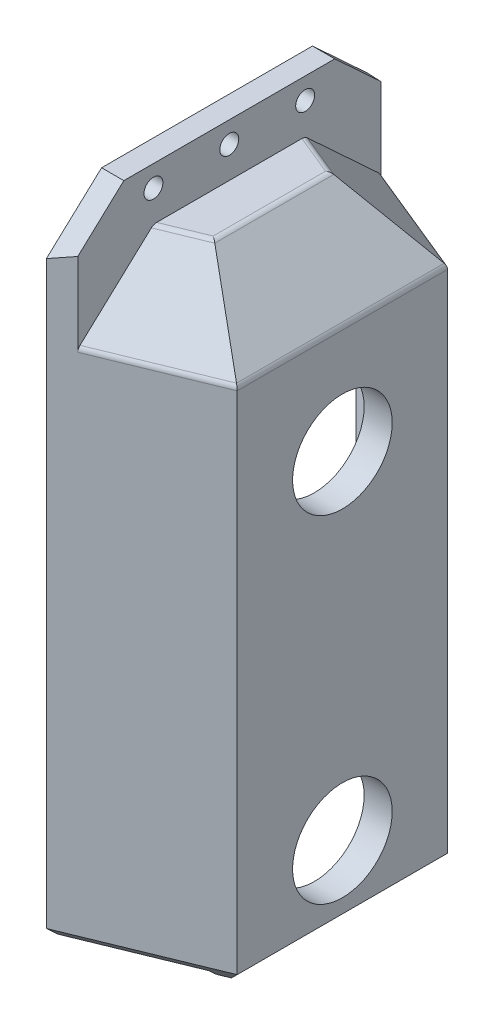
SolidWorks part; units mm, degrees
material "PLA"
ref_plane "Front Plane" through (0, 0, 0) normal (0, 0, 1) x (1, 0, 0)
ref_plane "Top Plane" through (0, 0, 0) normal (0, 1, 0) x (1, 0, 0)
ref_plane "Right Plane" through (0, 0, 0) normal (1, 0, 0) x (0, 0, -1)
sketch "Sketch1" plane through (0, 0, 0) normal (1, 0, 0) x (0, 0, -1)
  line L1 (-15, 2.5) -> (15, 2.5)
  line L2 (-15, 2.5) -> (-15, -2.5)
  line L3 (-15, -2.5) -> (15, -2.5)
  line L4 (15, 2.5) -> (15, -2.5)
  point P4 (0, 2.5)
  point P6 (-15, 0)
  dimension "D1" = 30
  dimension "D2" = 5
extrude "Boss-Extrude1" add sketch "Sketch1" along normal blind 19.3
sketch "Sketch2" plane through (0, 0, 0) normal (-1, 0, 0) x (0, 0, 1)
  line L0 (-20.4312, -2.5) -> (20.4312, -2.5) construction
  line L4 (15, 0) -> (20.5974, 0) construction
  line L5 (-19.4026, -2.5) -> (20.5974, -2.5)
  line L7 (-19.4026, 7.5) -> (20.5974, 7.5)
  line L8 (20.5974, -2.5) -> (20.5974, 7.5)
  line L9 (-19.4026, 7.5) -> (-19.4026, 2.5) construction
  line L11 (-19.4026, 7.5) -> (-19.4026, -2.5)
  line L12 (-19.4026, 0) -> (-15, 0) construction
  line L13 (-15, -2.5) -> (-15, 2.5) construction
  line L14 (15, 2.5) -> (15, -2.5) construction
  line L15 (-19.4026, 5) -> (0, 5) construction
  line L16 (20.5974, 5) -> (0, 5) construction
  point P3 (0, -2.5)
  point P6 (0, 2.5)
  point P12 (0, 0)
  dimension "D1" = 10
  dimension "D2" = 40
extrude "Boss-Extrude2" add sketch "Sketch2" against normal blind 3.175
sketch "Sketch3" plane through (0, -2.5, 0) normal (0, -1, 0) x (1, 0, 0)
  line L0 (19.3, -15) -> (3.175, -15) construction
  line L1 (19.3, 15) -> (15.3, 15)
  line L2 (19.3, 15) -> (19.3, -15)
  line L3 (19.3, -15) -> (15.3, -15)
  line L4 (15.3, 15) -> (15.3, -15)
  dimension "D1" = 4
extrude "Boss-Extrude3" add sketch "Sketch3" along normal blind 75
sketch "Sketch4" plane through (19.3, 0, 0) normal (1, 0, 0) x (0, 0, -1)
  line L0 (15, 2.5) -> (-15, 2.5) construction
  circle A0 centre (0, -17.9) radius 7.1
  circle A1 centre (0, -65.9) radius 7.1
  dimension "D1" = 14.2
  dimension "D2" = 14.2
  dimension "D3" = 20.4
  dimension "D4" = 48
extrude "Cut-Extrude1" cut sketch "Sketch4" against normal up to next
sketch "Sketch10" plane through (0, 2.5, 0) normal (0, 1, 0) x (1, 0, 0)
  line L0 (3.175, 19.4026) -> (0, 19.4026)
  line L1 (0, 19.4026) -> (0, 22.9026)
  line L2 (0, 22.9026) -> (19.3, 15)
  line L3 (19.3, 15) -> (3.175, 15) construction
  line L4 (19.3, 15) -> (19.3, -15) construction
  line L5 (3.175, 19.4026) -> (3.175, 15)
  line L6 (3.175, 15) -> (19.3, 15)
  dimension "D1" = 3.5
extrude "Boss-Extrude7" add sketch "Sketch10" against normal up to surface (5 mm away) up to face at (5.4125, -2.5, 0.2987)
sketch "Sketch11" plane through (0, 2.5, 0) normal (0, 1, 0) x (1, 0, 0)
  line L0 (0, 19.4026) -> (0, 22.9026)
  line L1 (0, 22.9026) -> (3.175, 21.6026)
  line L2 (19.3, 15) -> (0, 22.9026) construction
  line L3 (3.175, 21.6026) -> (3.175, 19.4026)
  line L4 (3.175, 19.4026) -> (0, 19.4026)
extrude "Boss-Extrude8" add sketch "Sketch11" along normal up to surface (5 mm away) up to face at (1.5875, 7.5, 0.5974)
ref_plane "Plane1" through (0, 0, 0) normal (0, 0, -1) x (-1, 0, 0)
mirror "Mirror2" about plane through (0, 0, 0) normal (0, 0, -1) of "Boss-Extrude8", "Boss-Extrude7"
chamfer "Chamfer1" distance 5 angle 45 1 edges at (3.175, 2.5, 0)
sketch "Sketch12" plane through (0, -2.5, 0) normal (0, -1, 0) x (1, 0, 0)
  line L0 (0, -22.9026) -> (19.3, -15)
  line L1 (19.3, -15) -> (15.3, -15)
  line L2 (15.3, -15) -> (0, -21.2648)
  line L3 (0, 22.9026) -> (0, -22.9026) construction
  line L4 (0, -21.2648) -> (0, -22.9026)
  line L5 (0, 22.9026) -> (19.3, 15)
  line L6 (19.3, 15) -> (15.3, 15)
  line L7 (15.3, 15) -> (0, 21.2648)
  line L8 (0, 21.2648) -> (0, 22.9026)
extrude "Boss-Extrude9" add sketch "Sketch12" along normal up to surface (75 mm away) up to face at (17.3, -77.5, 0)
sketch "Sketch13" plane through (0, 2.5, 0) normal (0, 1, 0) x (1, 0, 0)
  line L0 (3.175, 21.6026) -> (3.175, -21.6026)
  line L1 (3.175, -21.6026) -> (19.3, -15)
  line L2 (19.3, -15) -> (19.3, 15)
  line L3 (19.3, 15) -> (3.175, 21.6026)
extrude "Boss-Extrude10" add sketch "Sketch13" along normal up to surface (5 mm away) up to face at (1.5875, 7.5, 0)
chamfer "Chamfer2" distance 5 angle 45 3 edges at (7.65, -2.5, 18.1324) (7.65, -2.5, -18.1324) (15.3, -2.5, 0)
chamfer "Chamfer3" distance 10 angle 45 3 edges at (9.65, 7.5, -18.9513) (9.65, 7.5, 18.9513) (19.3, 7.5, 0)
sketch "Sketch14" plane through (0, 0, 0) normal (-1, 0, 0) x (0, 0, 1)
  line L15 (-22.9026, -2.5) -> (-22.9026, 7.7188)
  line L16 (22.9026, -2.5) -> (22.9026, 7.7188)
  line L18 (27.9967, 3.0046) -> (15.0346, 15)
  line L19 (15.0346, 15) -> (-15.0346, 15)
  line L20 (-15.0346, 15) -> (-27.9967, 3.0046)
  line L21 (22.9026, 7.7188) -> (15.0346, 15)
  line L22 (15.0346, 15) -> (-15.0346, 15)
  line L23 (-15.0346, 15) -> (-22.9026, 7.7188)
  line L29 (-22.9026, -2.5) -> (22.9026, -2.5)
  dimension "D1" = 7.5
extrude "Boss-Extrude15" add sketch "Sketch14" against normal blind 3.175
sketch "Sketch15" plane through (0, -2.5, 0) normal (0, -1, 0) x (1, 0, 0)
  line L3 (3.175, 22.9026) -> (0, 22.9026)
  line L4 (0, 22.9026) -> (3.175, 21.6026)
  line L5 (3.175, 21.6026) -> (3.175, 22.9026)
  line L6 (3.175, 22.9026) -> (0, 22.9026)
  line L7 (0, 22.9026) -> (3.175, 21.6026)
  line L8 (3.175, 21.6026) -> (3.175, 22.9026)
  line L9 (3.175, -22.9026) -> (3.175, -21.6026)
  line L10 (3.175, -21.6026) -> (0, -22.9026)
  line L11 (0, -22.9026) -> (3.175, -22.9026)
  line L12 (3.175, -22.9026) -> (3.175, -21.6026)
  line L13 (3.175, -21.6026) -> (0, -22.9026)
  line L14 (0, -22.9026) -> (3.175, -22.9026)
  dimension "D1" = 0
  dimension "D2" = 0
extrude "Cut-Extrude2" cut sketch "Sketch15" against normal through all
fillet "Fillet6" radius 1 3 edges at (6.2375, 7.5, -9.5428) (9.3, 7.5, 0) (6.2375, 7.5, 9.5428)
fillet "Fillet7" radius 1 3 edges at (11.2375, -2.5, -18.3013) (19.3, -2.5, 0) (11.2375, -2.5, 18.3013)
chamfer "Chamfer6" distance 2.5 angle 45 3 edges at (9.65, -77.5, -18.9513) (19.3, -77.5, 0) (9.65, -77.5, 18.9513)
sketch "Sketch16" plane through (3.175, 0, 0) normal (1, 0, 0) x (0, 0, -1)
  line L1 (-21.6026, 8.9219) -> (-15.0346, 15) construction
  line L2 (15.0346, 15) -> (21.6026, 8.9219) construction
  line L3 (-18.3186, 11.9609) -> (0, 11.9609) construction
  line L4 (0, 11.9609) -> (18.3186, 11.9609) construction
  circle A0 centre (0, 11.9609) radius 1.35
  circle A1 centre (-10.8186, 11.9609) radius 1.35
  circle A2 centre (10.8186, 11.9609) radius 1.35
  point P12 (0, 0)
  point P13 (0, 0)
  dimension "D1" = 2.7
  dimension "D2" = 2.7
  dimension "D3" = 2.7
  dimension "D4" = 7.5
  dimension "D5" = 7.5
extrude "Cut-Extrude3" cut sketch "Sketch16" against normal through all
